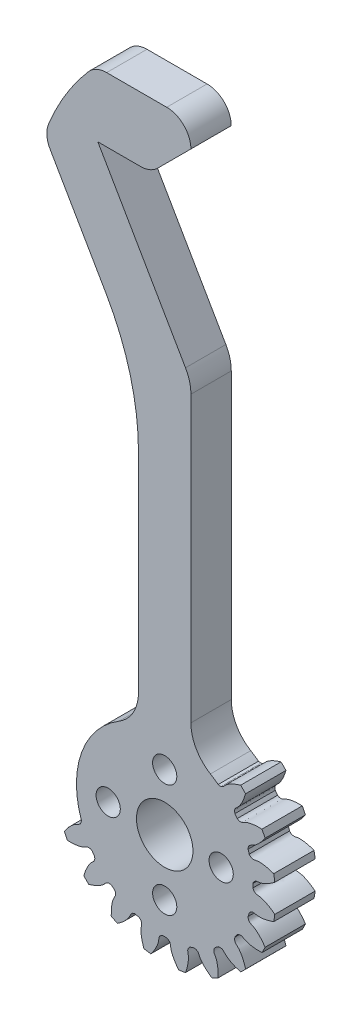
SolidWorks part; units mm, degrees
note: '?' marks a value the reader was unsure of.
material "聚脂树脂"
ref_plane "前视基准面" through (0, 0, 0) normal (0, 0, 1) x (1, 0, 0)
ref_plane "上视基准面" through (0, 0, 0) normal (0, 1, 0) x (1, 0, 0)
ref_plane "右视基准面" through (0, 0, 0) normal (1, 0, 0) x (0, 0, -1)
other "Configuration Table"
sketch "草图1" plane through (0, 0, 0) normal (0, 0, 1) x (1, 0, 0)
  circle A0 centre (0, 0) radius 13.75
extrude "凸台-拉伸1" add sketch "草图1" along normal blind 5
ref_axis "基准轴1" through (0, 0, -1.5) along (0, 0, 1)?
sketch "草图2" plane through (0, 0, 0) normal (0, 0, 1) x (1, 0, 0)
  line L0 (0, 0) -> (0, 13.75) construction
  circle A0 centre (0, 0) radius 13.75 construction
  arc A1 (0.2416, 10.9348) -> (-0.2416, 10.9348) centre (0, 0) ccw
  arc A2 (3.9764, 15.6228) -> (-3.9764, 15.6228) centre (0, 0) ccw
  spline S0 degree 3 poles (0.2416, 10.9348) (0.764, 11.1168) (0.6964, 11.4839) (0.7661, 11.8375) (0.7736, 11.8719) (0.7829, 11.9108) (0.7941, 11.954) (0.8075, 12.0015) (0.8231, 12.0532) (0.8413, 12.1091) (0.8621, 12.169) (0.8857, 12.2329) (0.9123, 12.3007) (0.9421, 12.3723) (0.9752, 12.4476) (1.0117, 12.5264) (1.0519, 12.6088) (1.0959, 12.6945) (1.1438, 12.7834) (1.1957, 12.8755) (1.2519, 12.9705) (1.3125, 13.0684) (1.3775, 13.1691) (1.4472, 13.2723) (1.5216, 13.3779) (1.601, 13.4858) (1.6853, 13.5958) (1.7747, 13.7078) (1.8694, 13.8216) (1.9693, 13.937) (2.0748, 14.0539) (2.1857, 14.1721) (2.3023, 14.2914) (2.4246, 14.4116) (2.5527, 14.5326) (2.6866, 14.6542) (2.8265, 14.7761) (2.9725, 14.8983) (3.1245, 15.0204) (3.2826, 15.1424) (3.4469, 15.2639) (3.6768, 15.427) (3.8549, 15.5454) (3.9764, 15.6228) knots 0 0 0 0 0.165916 0.170906 0.176664 0.183189 0.190482 0.198542 0.207371 0.216967 0.22733 0.238462 0.250361 0.263027 0.276462 0.290664 0.305634 0.321371 0.337876 0.355149 0.37319 0.391998 0.411574 0.431917 0.453028 0.474907 0.497554 0.520968 0.54515 0.570099 0.595817 0.622302 0.649554 0.677575 0.706363 0.735918 0.766242 0.797333 0.829191 0.861818 0.895212 0.929373 1 1 1 1
  spline S1 degree 3 poles (-0.2416, 10.9348) (-0.764, 11.1168) (-0.6964, 11.4839) (-0.7661, 11.8375) (-0.7736, 11.8719) (-0.7829, 11.9108) (-0.7941, 11.954) (-0.8075, 12.0015) (-0.8231, 12.0532) (-0.8413, 12.1091) (-0.8621, 12.169) (-0.8857, 12.2329) (-0.9123, 12.3007) (-0.9421, 12.3723) (-0.9752, 12.4476) (-1.0117, 12.5264) (-1.0519, 12.6088) (-1.0959, 12.6945) (-1.1438, 12.7834) (-1.1957, 12.8755) (-1.2519, 12.9705) (-1.3125, 13.0684) (-1.3775, 13.1691) (-1.4472, 13.2723) (-1.5216, 13.3779) (-1.601, 13.4858) (-1.6853, 13.5958) (-1.7747, 13.7078) (-1.8694, 13.8216) (-1.9693, 13.937) (-2.0748, 14.0539) (-2.1857, 14.1721) (-2.3023, 14.2914) (-2.4246, 14.4116) (-2.5527, 14.5326) (-2.6866, 14.6542) (-2.8265, 14.7761) (-2.9725, 14.8983) (-3.1245, 15.0204) (-3.2826, 15.1424) (-3.4469, 15.2639) (-3.6768, 15.427) (-3.8549, 15.5454) (-3.9764, 15.6228) knots 0 0 0 0 0.165916 0.170906 0.176664 0.183189 0.190482 0.198542 0.207371 0.216967 0.22733 0.238462 0.250361 0.263027 0.276462 0.290664 0.305634 0.321371 0.337876 0.355149 0.37319 0.391998 0.411574 0.431917 0.453028 0.474907 0.497554 0.520968 0.54515 0.570099 0.595817 0.622302 0.649554 0.677575 0.706363 0.735918 0.766242 0.797333 0.829191 0.861818 0.895212 0.929373 1 1 1 1
extrude "切除-拉伸1" cut sketch "草图2" along normal through all
pattern_circular "阵列(圆周)1" count 20 every 18 about axis through (0, 0, -1.5) along (0, 0, 1) of "切除-拉伸1"
sketch "草图6" plane through (0, 0, 0) normal (0, 0, -1) x (-1, 0, 0)
  line L0 (0, 0) -> (0, 65.9124) construction
  line L1 (0, 0) -> (39.45, 0) construction
  line L2 (0, 0) -> (-30.8379, 0) construction
  line L3 (-12.5, 0) -> (-12.5, 56.4778) construction
  line L4 (3.25, 0) -> (3.25, 36.0742)
  line L5 (-3.25, 0) -> (-3.25, 36.0742)
  line L6 (-3.25, 36.0742) -> (-3.25, 74.2415)
  line L7 (-3.25, 74.2415) -> (-12.5, 58.22) construction
  line L8 (-3.25, 74.2415) -> (6.3052, 90.7916) construction
  line L9 (-3.25, 74.2415) -> (1.0877, 81.7545)
  line L10 (-3.25, 0) -> (3.25, 0)
  line L11 (-5.8534, 12.4419) -> (-3.25, 13.9449)
  line L12 (5.8534, 12.4419) -> (3.25, 13.9449)
  line L13 (-12.5, 82.22) -> (-33.2846, 46.22)
  line L14 (-33.2846, 46.22) -> (8.2846, 46.22)
  line L15 (8.2846, 46.22) -> (-12.5, 82.22)
  line L16 (-3.25, 78.1985) -> (14.4573, 47.5286)
  line L17 (8.2846, 70.22) -> (-12.5, 34.22)
  line L18 (-12.5, 34.22) -> (-33.2846, 70.22)
  line L19 (-33.2846, 70.22) -> (8.2846, 70.22)
  line L20 (3.25, 36.0742) -> (3.25, 40.111)
  line L21 (3.25, 40.111) -> (3.25, 47.4998)
  line L22 (-3.25, 78.1985) -> (8.5204, 78.1985)
  line L23 (3.25, 47.4998) -> (-2.8122, 50.9998)
  line L24 (14.9089, 67.6937) -> (3.25, 47.4998)
  line L25 (-3.25, 74.2415) -> (-3.25, 78.1985)
  circle A0 centre (0, 0) radius 12.5 construction
  circle A1 centre (-12.5, 58.22) radius 24 construction
  circle A2 centre (-12.5, 58.22) radius 27.1754 construction
  arc A3 (1.0877, 81.7545) -> (3.25, 36.0742) centre (-12.5, 58.22) cw
  arc A4 (-0.5, 79.0046) -> (-3.25, 36.0742) centre (-12.5, 58.22) cw
  arc A5 (3.25, 33.8697) -> (14.4573, 47.5286) centre (-12.5, 58.22) ccw
  arc A6 (7.7846, 47.086) -> (7.2846, 46.22) centre (8.2846, 46.22) cw
  arc A7 (2, 83.3347) -> (14.9089, 67.6937) centre (-12.5, 58.22) cw
  spline S0 degree 3 poles (5837.5155, 3864.2395) (-49.1578, -29.6908) (-0.8621, 4.7049) (-4.3931, 11.033) (-4.4189, 11.076) (-4.4589, 11.1387) (-4.5098, 11.2131) (-4.5827, 11.3111) (-4.6712, 11.4208) (-4.7765, 11.541) (-4.8994, 11.6706) (-5.0408, 11.8083) (-5.2016, 11.9528) (-5.3825, 12.1027) (-5.5474, 12.2287) (-5.6899, 12.331) (-35.2983, 32.707) (-218.0349, -174.3414) (6459.0271, 2694.747) knots -3.368657 -3.368657 -3.368657 -3.368657 0.165916 0.170906 0.183189 0.190482 0.207371 0.22733 0.250361 0.276462 0.305634 0.337876 0.37319 0.411574 0.453028 0.474907 0.497554 18.069832 18.069832 18.069832 18.069832 only from (-3.6089, 10.325) to (-5.8534, 12.4419) construction
  spline S1 degree 3 poles (-3.25, 10.3561) (-4.1482, 10.2029) (-4.1808, 10.6525) (-4.3931, 11.033) (-4.4189, 11.076) (-4.4589, 11.1387) (-4.5098, 11.2131) (-4.5827, 11.3111) (-4.6712, 11.4208) (-4.7765, 11.541) (-4.8994, 11.6706) (-5.0408, 11.8083) (-5.2016, 11.9528) (-5.3825, 12.1027) (-5.5842, 12.2567) (-5.7442, 12.3691) (-5.8366, 12.4308) (-5.8534, 12.4419) knots -0.030413 -0.030413 -0.030413 -0.030413 0.165916 0.170906 0.183189 0.190482 0.207371 0.22733 0.250361 0.276462 0.305634 0.337876 0.37319 0.411574 0.453028 0.497554 0.507432 0.507432 0.507432 0.507432
  spline S2 degree 3 poles (-5837.5155, 3864.2395) (49.1578, -29.6908) (0.8621, 4.7049) (4.3931, 11.033) (4.4189, 11.076) (4.4589, 11.1387) (4.5098, 11.2131) (4.5827, 11.3111) (4.6712, 11.4208) (4.7765, 11.541) (4.8994, 11.6706) (5.0408, 11.8083) (5.2016, 11.9528) (5.3825, 12.1027) (5.5474, 12.2287) (5.6899, 12.331) (35.2983, 32.707) (218.0349, -174.3414) (-6459.0271, 2694.747) knots -2.876089 -2.876089 -2.876089 -2.876089 0.658484 0.663474 0.675757 0.68305 0.699939 0.719899 0.742929 0.76903 0.798202 0.830445 0.865758 0.904142 0.945597 0.967475 0.990122 18.5624 18.5624 18.5624 18.5624 only from (3.6089, 10.325) to (5.8534, 12.4419) construction
  spline S3 degree 3 poles (3.25, 10.3561) (4.1482, 10.2029) (4.1808, 10.6525) (4.3931, 11.033) (4.4189, 11.076) (4.4589, 11.1387) (4.5098, 11.2131) (4.5827, 11.3111) (4.6712, 11.4208) (4.7765, 11.541) (4.8994, 11.6706) (5.0408, 11.8083) (5.2016, 11.9528) (5.3825, 12.1027) (5.5842, 12.2567) (5.7442, 12.3691) (5.8366, 12.4308) (5.8534, 12.4419) knots 0.462155 0.462155 0.462155 0.462155 0.658484 0.663474 0.675757 0.68305 0.699939 0.719899 0.742929 0.76903 0.798202 0.830445 0.865758 0.904142 0.945597 0.990122 1 1 1 1
  dimension "D1" = 25
  dimension "D4" = 48
  dimension "D5" = 30
  dimension "D8" = 60
  dimension "D10" = 29
  dimension "D11" = 1
  dimension "D12" = 29
  dimension "D2" = 6.5
  dimension "D3" = 58.22
  dimension "D6" = 60
  dimension "D7" = 60
  dimension "D9" = 6
  dimension "D13" = 7
extrude "凸台-拉伸2" add sketch "草图6" against normal blind 5
ref_plane "基准面1" through (12.5, 0, 0) normal (1, 0, 0) x (0, 0, -1)
sketch "草图4" plane through (0, 0, 5) normal (0, 0, 1) x (1, 0, 0)
  line L0 (0, 0) -> (0, 14.4175) construction
  line L1 (0, 0) -> (19.7904, 0) construction
  circle A0 centre (0, 0) radius 9
  circle A1 centre (0, 0) radius 3.5
  circle A2 centre (0, 7) radius 1.5
  circle A3 centre (7, 0) radius 1.5
  circle A4 centre (0, -7) radius 1.5
  circle A5 centre (-7, 0) radius 1.5
  dimension "D1" = 18
  dimension "D2" = 7
  dimension "D3" = 3
  dimension "D4" = 3
  dimension "D5" = 7
  dimension "D6" = 7
extrude "切除-拉伸2" cut sketch "草图4" against normal blind 20 contours A1 | A5 | A2 | A3 | A4
ref_plane "基准面2" through (0, 0, 9) normal (0, 0, 1) x (1, 0, 0)
sketch "草图17" plane through (0, 0, 5) normal (0, 0, 1) x (1, 0, 0)
  line L0 (0, 0) -> (-6.6228, 8.7044)
  line L1 (-6.6228, 8.7044) -> (-11.857, 15.5837)
  line L2 (0, 0) -> (-10.325, -3.6089)
  line L3 (-10.325, -3.6089) -> (-17.9409, -6.2709)
  circle A0 centre (0, 0) radius 10.9375
  arc A1 (-6.2318, 8.9885) -> (-6.6228, 8.7044) centre (0, 0) ccw construction
  circle A2 centre (0, 0) radius 17.5
  dimension "D1" = 35
extrude "切除-拉伸5" cut sketch "草图17" against normal blind 10 contours L1 A2 L3 A0
sketch "草图20" plane through (0, 0, 0) normal (0, 0, -1) x (-1, 0, 0)
  line L0 (-3.25, 13.9449) -> (-3.25, 10.4435)
  line L1 (3.25, 13.9449) -> (3.25, 10.4435)
  line L2 (5.8534, 12.4419) -> (3.25, 13.9449) construction
  line L3 (-5.8534, 12.4419) -> (-3.25, 13.9449) construction
  line L4 (5.8534, 12.4419) -> (3.25, 13.9449)
  line L5 (-5.8534, 12.4419) -> (-3.25, 13.9449)
  circle A0 centre (0, 0) radius 10.9375
  arc A1 (10.325, -3.6089) -> (6.2318, 8.9885) centre (0, 0) ccw construction
  arc A2 (6.6252, 12.0486) -> (5.8534, 12.4419) centre (0, 0) ccw construction
  arc A3 (-5.8534, 12.4419) -> (-6.6252, 12.0486) centre (0, 0) ccw construction
  arc A4 (6.6252, 12.0486) -> (5.8534, 12.4419) centre (0, 0) ccw
  arc A5 (-5.8534, 12.4419) -> (-6.6252, 12.0486) centre (0, 0) ccw
  spline S0 degree 3 poles (940.4852, -347.6041) (-11.6727, 10.1742) (4.7326, 6.5586) (6.3437, 10.0391) (6.3633, 10.0853) (6.3905, 10.1545) (6.4208, 10.2394) (6.4573, 10.356) (6.4939, 10.4921) (6.5293, 10.6479) (6.5619, 10.8235) (6.5902, 11.0188) (6.6126, 11.2338) (6.6276, 11.4683) (6.6325, 11.6758) (6.6315, 11.8512) (6.1325, 31.3668) (-75.0291, 47.9678) (845.3646, -532.4841) knots -1.696649 -1.696649 -1.696649 -1.696649 0.165916 0.170906 0.183189 0.190482 0.207371 0.22733 0.250361 0.276462 0.305634 0.337876 0.37319 0.411574 0.453028 0.474907 0.497554 10.021595 10.021595 10.021595 10.021595 only from (6.2318, 8.9885) to (6.6252, 12.0486) construction
  spline S1 degree 3 poles (-940.4852, -347.6041) (11.6727, 10.1742) (-4.7326, 6.5586) (-6.3437, 10.0391) (-6.3633, 10.0853) (-6.3905, 10.1545) (-6.4208, 10.2394) (-6.4573, 10.356) (-6.4939, 10.4921) (-6.5293, 10.6479) (-6.5619, 10.8235) (-6.5902, 11.0188) (-6.6126, 11.2338) (-6.6276, 11.4683) (-6.6325, 11.6758) (-6.6315, 11.8512) (-6.1325, 31.3668) (75.0291, 47.9678) (-845.3646, -532.4841) knots -1.204081 -1.204081 -1.204081 -1.204081 0.658484 0.663474 0.675757 0.68305 0.699939 0.719899 0.742929 0.76903 0.798202 0.830445 0.865758 0.904142 0.945597 0.967475 0.990122 10.514164 10.514164 10.514164 10.514164 only from (-6.2318, 8.9885) to (-6.6252, 12.0486) construction
  spline S2 degree 3 poles (6.2318, 8.9885) (5.9162, 9.4428) (6.1867, 9.7) (6.3437, 10.0391) (6.3633, 10.0853) (6.3905, 10.1545) (6.4208, 10.2394) (6.4573, 10.356) (6.4939, 10.4921) (6.5293, 10.6479) (6.5619, 10.8235) (6.5902, 11.0188) (6.6126, 11.2338) (6.6276, 11.4683) (6.6336, 11.722) (6.6305, 11.9176) (6.6261, 12.0285) (6.6252, 12.0486) knots 0 0 0 0 0.165916 0.170906 0.183189 0.190482 0.207371 0.22733 0.250361 0.276462 0.305634 0.337876 0.37319 0.411574 0.453028 0.497554 0.507432 0.507432 0.507432 0.507432
  spline S3 degree 3 poles (-6.2318, 8.9885) (-5.9162, 9.4428) (-6.1867, 9.7) (-6.3437, 10.0391) (-6.3633, 10.0853) (-6.3905, 10.1545) (-6.4208, 10.2394) (-6.4573, 10.356) (-6.4939, 10.4921) (-6.5293, 10.6479) (-6.5619, 10.8235) (-6.5902, 11.0188) (-6.6126, 11.2338) (-6.6276, 11.4683) (-6.6336, 11.722) (-6.6305, 11.9176) (-6.6261, 12.0285) (-6.6252, 12.0486) knots 0.492568 0.492568 0.492568 0.492568 0.658484 0.663474 0.675757 0.68305 0.699939 0.719899 0.742929 0.76903 0.798202 0.830445 0.865758 0.904142 0.945597 0.990122 1 1 1 1
extrude "切除-拉伸7" cut sketch "草图20" against normal blind 10 contours S3 A0 L0 L5 A5 | A0 S2 A4 L4 L1
fillet "圆角7" radius 5 2 edges at (-3.25, 10.4435, 2.5) (3.25, 10.4435, 2.5)
fillet "圆角8" radius 30 1 edges at (-3.25, 47.4998, 2.5)
fillet "圆角9" radius 3 3 edges at (-14.9089, 67.6937, 2.5) (-8.5204, 78.1985, 2.5) (3.25, 78.1985, 2.5)
chamfer "倒角1" distance 5 angle 45 1 edges at (3.25, 70.22, 2.5)
fillet "圆角10" radius 5 1 edges at (3.25, 50.2415, 2.5)
fillet "圆角11" radius 3 1 edges at (-1.75, 70.22, 2.5)
